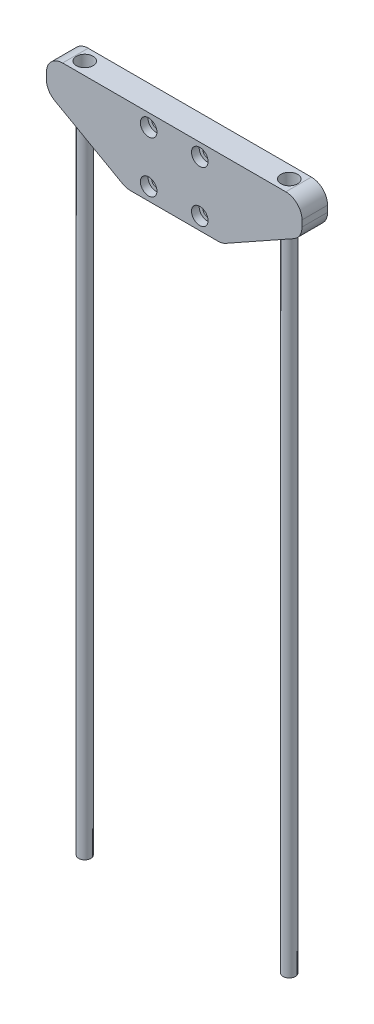
SolidWorks part; units mm, degrees
other "Markup2"
sketch "Sketch8"
other "Markup3"
sketch "Sketch15"
ref_plane "Front Plane" through (0, 0, 0) normal (0, 0, 1) x (1, 0, 0)
ref_plane "Top Plane" through (0, 0, 0) normal (0, 1, 0) x (1, 0, 0)
ref_plane "Right Plane" through (0, 0, 0) normal (1, 0, 0) x (0, 0, -1)
sketch "Sketch2" plane through (0, 0, 0) normal (0, 0, 1) x (1, 0, 0)
  line L0 (-40, 0) -> (-40, -254) construction
  line L1 (40, 0) -> (40, -254) construction
  line L2 (0, 48.6067) -> (0, -93.2297) construction
  line L3 (-50, 15) -> (-50, 2.5)
  line L4 (-50, 2.5) -> (-18.75, -15)
  line L5 (-18.75, -15) -> (18.75, -15)
  line L6 (18.75, -15) -> (50, 2.5)
  line L7 (-50, 15) -> (50, 15)
  line L8 (50, 15) -> (50, 2.5)
  line L10 (-42.3812, 0) -> (-37.6188, 0)
  line L11 (-42.3812, 0) -> (-42.3812, -254)
  line L12 (-42.3812, -254) -> (-37.6187, -254)
  line L13 (-37.6188, 0) -> (-37.6187, -254)
  line L14 (-10, 10) -> (10, 10) construction
  line L15 (-10, 10) -> (-10, -10) construction
  line L16 (-10, -10) -> (10, -10) construction
  line L17 (10, 10) -> (10, -10) construction
  line L18 (37.6188, -254) -> (42.3813, -254)
  line L19 (37.6188, -254) -> (37.6188, 0)
  line L20 (37.6188, 0) -> (42.3812, 0)
  line L21 (42.3813, -254) -> (42.3812, 0)
  dimension "D1" = 80
  dimension "D2" = 254
  dimension "D3" = 4.7625
  dimension "D4" = 20
  dimension "D5" = 20
  dimension "D7" = 15
  dimension "D8" = 15
  dimension "D9" = 5
  dimension "D10" = 12.5
  dimension "D11" = 100
  dimension "D12" = 37.5
sketch "Sketch9" plane through (0, 0, 0) normal (0, 1, 0) x (1, 0, 0)
  line L0 (-40, 0) -> (-35, 0) construction
  line L2 (-40, 2.3812) -> (-35, 2.3812)
  line L3 (-40, -2.3812) -> (-35, -2.3812)
  line L4 (0, 20.7896) -> (0, -26.7229) construction
  line L5 (40, 0) -> (35, 0) construction
  line L6 (40, 2.3813) -> (35, 2.3813)
  line L7 (40, -2.3813) -> (35, -2.3813)
  line L8 (-37.5, 2.3812) -> (-37.5, -2.3812) construction
  line L9 (-42.3812, 0) -> (-37.6187, 0) construction
  line L10 (37.5, 2.3813) -> (37.5, -2.3813) construction
  arc A0 (-40, 2.3812) -> (-40, -2.3812) centre (-40, 0) ccw
  arc A1 (-35, -2.3812) -> (-35, 2.3812) centre (-35, 0) ccw
  arc A2 (40, 2.3813) -> (40, -2.3813) centre (40, 0) cw
  arc A3 (35, -2.3813) -> (35, 2.3813) centre (35, 0) cw
  circle A4 centre (-40, 0) radius 1.5
  circle A5 centre (40, 0) radius 1.5
  point P5 (-37.5, 0)
  point P15 (37.5, 0)
  dimension "D1" = 5
  dimension "D3" = 3
  dimension "D2" = 4.7625
sketch "Sketch3" plane through (0, 0, 0) normal (0, 0, 1) x (1, 0, 0)
  line L0 (-50, 15) -> (-50, 2.5) construction
  line L1 (-50, 2.5) -> (-18.75, -15) construction
  line L2 (-18.75, -15) -> (18.75, -15) construction
  line L3 (18.75, -15) -> (50, 2.5) construction
  line L4 (50, 15) -> (50, 2.5) construction
  line L5 (-50, 15) -> (50, 15) construction
  line L6 (-50, 15) -> (-50, 2.5)
  line L7 (-50, 2.5) -> (-18.75, -15)
  line L8 (-18.75, -15) -> (18.75, -15)
  line L9 (18.75, -15) -> (50, 2.5)
  line L10 (50, 15) -> (50, 2.5)
  line L11 (-50, 15) -> (50, 15)
extrude "Boss-Extrude1" add sketch "Sketch3" along normal mid plane 10
sketch "Sketch10" plane through (0, 0, 0) normal (0, 1, 0) x (1, 0, 0)
  line L0 (40, 2.3813) -> (35, 2.3813) construction
  line L1 (40, -2.3813) -> (35, -2.3813) construction
  line L2 (-40, 2.3812) -> (-35, 2.3812) construction
  line L3 (-40, -2.3812) -> (-35, -2.3812) construction
  line L4 (40, 2.3813) -> (35, 2.3813)
  line L5 (40, -2.3813) -> (35, -2.3813)
  line L6 (-40, 2.3812) -> (-35, 2.3812)
  line L7 (-40, -2.3812) -> (-35, -2.3812)
  arc A0 (35, 2.3813) -> (35, -2.3813) centre (35, 0) ccw construction
  arc A1 (40, -2.3813) -> (40, 2.3813) centre (40, 0) ccw construction
  arc A2 (-35, -2.3812) -> (-35, 2.3812) centre (-35, 0) ccw construction
  arc A3 (-40, 2.3812) -> (-40, -2.3812) centre (-40, 0) ccw construction
  arc A4 (35, 2.3813) -> (35, -2.3813) centre (35, 0) ccw
  arc A5 (40, -2.3813) -> (40, 2.3813) centre (40, 0) ccw
  arc A6 (-35, -2.3812) -> (-35, 2.3812) centre (-35, 0) ccw
  arc A7 (-40, 2.3812) -> (-40, -2.3812) centre (-40, 0) ccw
extrude "Cut-Extrude1" cut sketch "Sketch10" against normal blind 10
sketch "Sketch4" plane through (0, 0, 0) normal (0, 0, 1) x (1, 0, 0)
  line L0 (40, 0) -> (40, -254) construction
  line L1 (-40, 0) -> (-40, -254) construction
  line L2 (-42.3812, 0) -> (-42.3812, -254) construction
  line L3 (-42.3812, -254) -> (-37.6187, -254) construction
  line L4 (-37.6188, 0) -> (-37.6187, -254) construction
  line L5 (-42.3812, 0) -> (-37.6188, 0) construction
  line L6 (40, 0) -> (40, -254)
  line L7 (-40, 0) -> (-40, -254)
  line L8 (-42.3812, 0) -> (-42.3812, -254)
  line L9 (-42.3812, -254) -> (-40, -254)
  line L10 (-37.6188, 0) -> (-37.6187, -254) construction
  line L11 (-42.3812, 0) -> (-40, 0)
  line L12 (-40, -254) -> (-40, -275.6996) construction
  line L13 (-40, -254) -> (-37.6187, -254) construction
  line L14 (-40, 0) -> (-37.6188, 0) construction
  line L15 (40, -254) -> (40, -281.3243) construction
  line L16 (37.6188, -254) -> (42.3813, -254)
  line L17 (37.6188, -254) -> (37.6188, 0)
  line L18 (37.6188, 0) -> (42.3812, 0)
  line L19 (42.3813, -254) -> (42.3812, 0)
  line L20 (37.6188, -247.4505) -> (40, -247.4505) construction
revolve "Revolve1" add sketch "Sketch4" angle 360 about L12 region at (-41.1906, -127, 0)
revolve "Revolve2" add sketch "Sketch4<3>" angle 360 about L15 region at (38.8094, -127, 0)
sketch "Sketch4<3>" plane through (0, 0, 0) normal (0, 0, 1) x (1, 0, 0) same geometry as "Sketch4"
hole_wizard "CBORE for M3 SHCS1" positions "Sketch5" profile "Sketch6" counterbore size "M3" standard "ANSI Metric"
sketch "Sketch5" plane through (0, 0, 5) normal (0, 0, 1) x (1, 0, 0)
  point P0 (-10, 10)
  point P3 (-10, -10)
  point P6 (10, -10)
  point P9 (10, 10)
sketch "Sketch6" plane through (-10, 10, 5) normal (1, 0, 0) x (0, -1, 0)
  line L0 (0, 0) -> (0, 8.5815)
  line L1 (0, 8.5815) -> (1.8, 7.5)
  line L2 (1.8, 7.5) -> (1.8, 3)
  line L3 (1.8, 3) -> (3.25, 3)
  line L4 (3.25, 3) -> (3.25, 0)
  line L5 (3.25, 0) -> (0, 0)
  line L10 (0, 8.5815) -> (-1.8, 7.5) construction
  line L11 (0, -6.35) -> (0, 107.95) construction
  dimension "Hole Dia." = 3.6
  dimension "Hole Depth" = 7.5
  dimension "C'Bore Dia." = 6.5
  dimension "C'Bore Depth" = 3
  dimension "Drill Angle" = 118
hole_wizard "CBORE for M3 SHCS2" positions "Sketch11" profile "Sketch12" counterbore size "M3" standard "ANSI Metric" end condition through all
sketch "Sketch11" plane through (0, 15, 0) normal (0, 1, 0) x (1, 0, 0)
  point P0 (-40, 0)
  point P3 (40, 0)
sketch "Sketch12" plane through (-40, 15, 0) normal (1, 0, 0) x (0, 0, 1)
  line L0 (0, 0) -> (0, 269)
  line L1 (0, 269) -> (1.8, 269)
  line L3 (1.8, 269) -> (1.8, 11)
  line L4 (1.8, 11) -> (3.25, 11)
  line L5 (3.25, 11) -> (3.25, 0)
  line L7 (3.25, 0) -> (0, 0)
  line L11 (0, -6.35) -> (0, 107.95) construction
  dimension "Thru Hole Dia." = 3.6
  dimension "Thru Hole Depth" = 269
  dimension "C'Bore Dia." = 6.5
  dimension "C'Bore Depth" = 11
hole_wizard "M3x0.5 Tapped Hole1" positions "Sketch13" profile "Sketch14" tap size "M3x0.5" standard "ANSI Metric"
sketch "Sketch13" plane through (0, 0, 0) normal (0, 1, 0) x (1, 0, 0)
  point P0 (-40, 0)
  point P3 (40, 0)
sketch "Sketch14" plane through (-40, 0, 0) normal (1, 0, 0) x (0, 0, 1)
  line L0 (0, 0) -> (0, 8.2511)
  line L1 (0, 8.2511) -> (1.25, 7.5)
  line L2 (1.25, 7.5) -> (1.25, 0)
  line L5 (1.25, 0) -> (0, 0)
  line L10 (0, 8.2511) -> (-1.25, 7.5) construction
  line L11 (0, -6.35) -> (0, 107.95) construction
  dimension "Tap Drill Dia." = 2.5
  dimension "Tap Drill Depth" = 7.5
  dimension "Drill Angle" = 118
fillet "Fillet1" radius 6.35 6 edges at (-18.75, -15, 0) (18.75, -15, 0) (50, 2.5, 0) (50, 15, 0) (-50, 15, 0) (-50, 2.5, 0)
